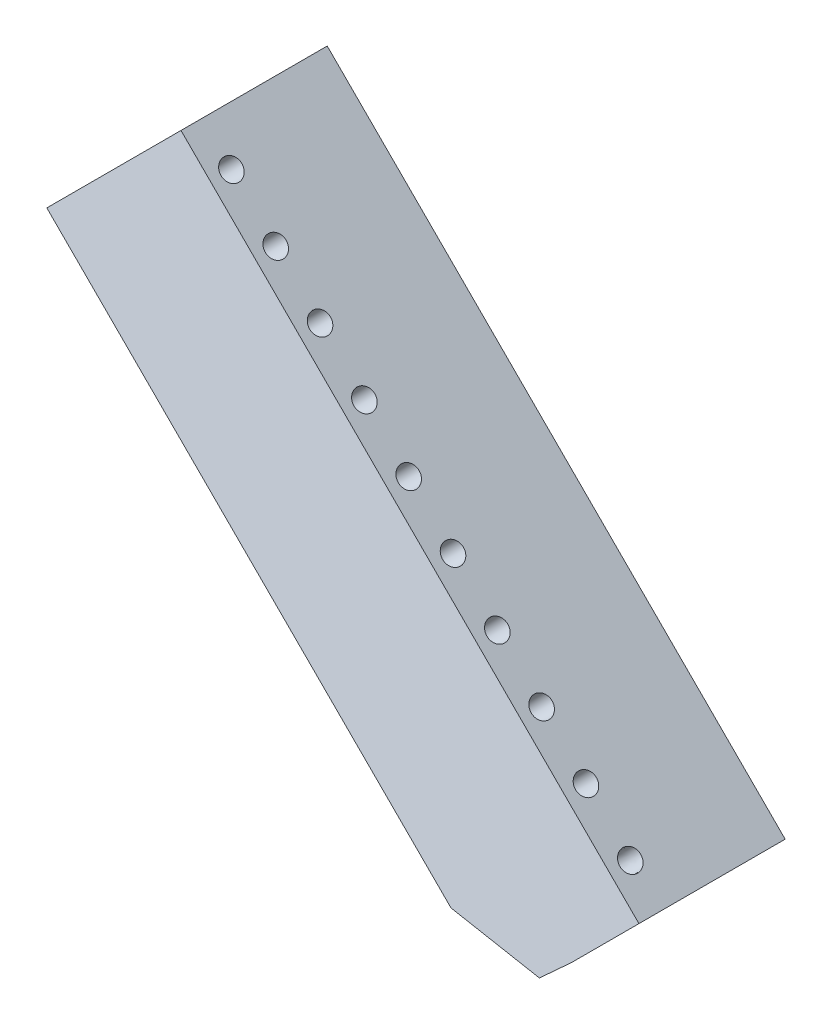
SolidWorks part; units mm, degrees
ref_plane "Alzado" through (0, 0, 0) normal (0, 0, 1) x (1, 0, 0)
ref_plane "Planta" through (0, 0, 0) normal (0, 1, 0) x (1, 0, 0)
ref_plane "Vista lateral" through (0, 0, 0) normal (1, 0, 0) x (0, 0, -1)
sketch "Croquis1" plane through (0, 0, 0) normal (0, 0, 1) x (1, 0, 0)
  line L0 (-48.4035, 23.3685) -> (-30.0187, 4.9837) construction
  line L1 (-30.0187, 4.9837) -> (-28.2509, 6.7514) construction
  line L2 (-48.4035, 23.3685) -> (-50.0929, 25.2112) construction
  line L3 (-30.0187, 4.9837) -> (-28.2509, 3.2159) construction
  line L4 (-28.2509, 3.2159) -> (-26.4832, 4.9837)
  line L5 (-26.4832, 4.9837) -> (-48.4035, 26.904)
  line L6 (-48.4035, 26.904) -> (-51.939, 23.3685)
  line L7 (-51.939, 23.3685) -> (-32.5932, 4.0226)
  line L8 (-32.5932, 4.0226) -> (-29.1348, 2.4604)
  line L9 (-29.1348, 2.4604) -> (-28.2509, 3.2159)
  circle A0 centre (-48.4035, 23.3685) radius 1.6
  circle A1 centre (-30.0187, 4.9837) radius 1.6
  dimension "D4" = 3.2
  dimension "D5" = 3.2
  dimension "D1" = 2.5
  dimension "D2" = 2.5
  dimension "D3" = 2.5
extrude "Saliente-Extruir1" add sketch "Croquis1" along normal blind 5
sketch "Croquis2" plane through (-37.6537, 37.6537, 0) normal (-0.7071, 0.7071, 0) x (0, 0, 1)
  line L2 (5, -20.2024) -> (5, -15.2024)
  line L3 (5, -15.2024) -> (7, -15.2024)
  line L4 (7, -15.2024) -> (9.8868, -20.2024)
  line L6 (9.8868, -20.2024) -> (5, -20.2024)
  dimension "D1" = 2
  dimension "D2" = 30
extrude "Saliente-Extruir2" add sketch "Croquis2" against normal up to vertex (31 mm away) up to point (-28.2509, 3.2159, 5)
sketch "Croquis3" plane through (-10.7497, -10.7497, 0) normal (0.7071, 0.7071, 0) x (0, 0, -1)
  line L0 (-7, 22.2504) -> (-7, 53.2504) construction
  line L1 (-7, 22.2504) -> (0, 22.2504) construction
  circle A0 centre (-6, 24.2504) radius 0.5
  circle A1 centre (-6, 27.2504) radius 0.5
  circle A2 centre (-6, 30.2504) radius 0.5
  circle A3 centre (-6, 33.2504) radius 0.5
  circle A4 centre (-6, 36.2504) radius 0.5
  circle A5 centre (-6, 39.2504) radius 0.5
  circle A6 centre (-6, 42.2504) radius 0.5
  circle A7 centre (-6, 45.2504) radius 0.5
  circle A8 centre (-6, 48.2504) radius 0.5
  circle A9 centre (-6, 51.2504) radius 0.5
  dimension "D1" = 1
  dimension "D2" = 1
  dimension "D3" = 2
  dimension "D4" = 10
extrude "Cortar-Extruir1" cut sketch "Croquis3" along direction (0.6124, 0.6124, -0.5) on the side against the normal up to surface (5 mm away) up to face at (-38.1836, 9.6131, 4.9623)
sketch "Croquis4" plane through (0, 0, 0) normal (0, 0, -1) x (-1, 0, 0)
  line L0 (32.5932, 4.0226) -> (30.0187, 1.4481)
  line L1 (30.0187, 1.4481) -> (28.2509, 3.2159)
  line L2 (28.2509, 3.2159) -> (29.1348, 2.4604)
  line L3 (29.1348, 2.4604) -> (32.5932, 4.0226)
extrude "Cortar-Extruir2" cut sketch "Croquis4" against normal up to vertex (9.8868 mm away) up to point (-30.0187, 1.4481, 9.8868)
